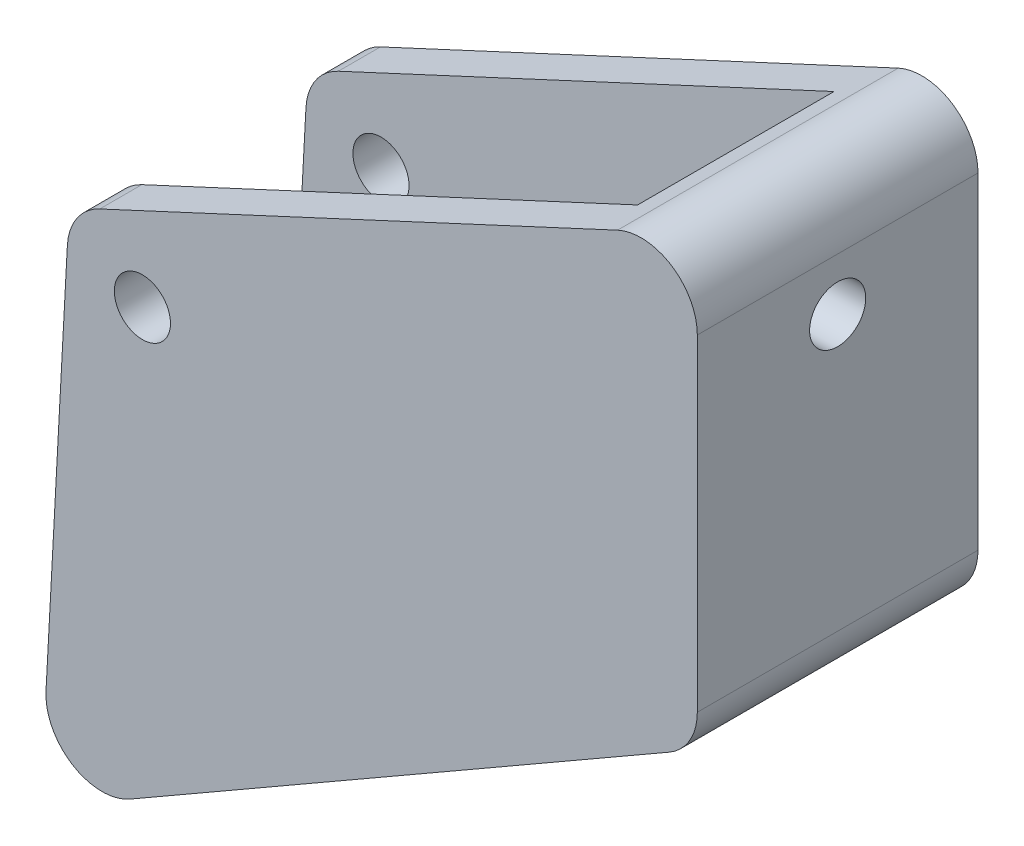
SolidWorks part; units mm, degrees
ref_plane "Plan de face" through (0, 0, 0) normal (0, 0, 1) x (1, 0, 0)
ref_plane "Plan de dessus" through (0, 0, 0) normal (0, 1, 0) x (1, 0, 0)
ref_plane "Plan de droite" through (0, 0, 0) normal (1, 0, 0) x (0, 0, -1)
sketch "Esquisse1" plane through (0, 0, 0) normal (0, 0, 1) x (1, 0, 0)
  line L0 (-16.8159, -61.1738) -> (115.7116, 0.3875) construction
  line L1 (-13.044, 8.8262) -> (98.8497, 60.8028)
  line L2 (-13.044, 8.8262) -> (-18.163, -86.1738)
  line L3 (98.8497, 60.8028) -> (138.7039, -24.9944) construction
  line L4 (-18.163, -86.1738) -> (98.8497, -18.8459)
  line L5 (98.8497, -18.8459) -> (98.8497, 60.8028)
  line L6 (0, 0) -> (0, 59.2463) construction
  dimension "D2" = 70
  dimension "D3" = 62
  dimension "D4" = 13.5
  dimension "D5" = 95
  dimension "D6" = 135
  dimension "D7" = 57
  dimension "D9" = 13.5
  dimension "D10" = 79.6487
extrude "Boss.-Extru.2" add sketch "Esquisse1" along normal mid plane 50 contours L4 L5 L1 L2 region at (40.2075, -9.8823, 0)
sketch "Esquisse2" plane through (0, 0, 0) normal (0, 0, 1) x (1, 0, 0)
  line L0 (-16.8159, -61.1738) -> (82.9463, -14.8325)
  line L1 (-13.044, 8.8262) -> (80.7111, 52.3771)
  line L2 (-13.044, 8.8262) -> (-16.8159, -61.1738)
  line L3 (80.7111, 52.3771) -> (120.1069, -32.4332) construction
  line L5 (82.9463, -14.8325) -> (80.7111, 52.3771)
  line L6 (-13.044, 8.8262) -> (98.8497, 60.8028) construction
  line L7 (-13.044, 8.8262) -> (-18.163, -86.1738) construction
  dimension "D1" = 20
  dimension "D2" = 70
  dimension "D3" = 62
  dimension "D6" = 110
extrude "Enlèv. mat.-Extru.1" cut sketch "Esquisse2" against normal mid plane 35
sketch "Esquisse3" plane through (0, 0, 25) normal (0, 0, 1) x (1, 0, 0)
  line L0 (0, 0) -> (0, 40.5336) construction
  line L1 (-13.044, 8.8262) -> (98.8497, 60.8028) construction
  line L2 (-13.044, 8.8262) -> (-18.163, -86.1738) construction
  circle A0 centre (0, 0) radius 5
  point P2 (0, 32.55)
  dimension "D3" = 10
  dimension "D1" = 13.5
  dimension "D2" = 13.5
  dimension "D4" = 32.55
extrude "Enlèv. mat.-Extru.2" cut sketch "Esquisse3" against normal through all
fillet "Congé1" radius 10 2 edges at (-13.044, 8.8262, -21.25) (-13.044, 8.8262, 21.25)
fillet "Congé2" radius 10 1 edges at (-18.163, -86.1738, 0)
fillet "Congé3" radius 10 2 edges at (98.8497, 60.8028, 0) (98.8497, -18.8459, 0)
ref_axis "Axez" through (0, 0, 0) along (0, 0, 1)
ref_axis "Axe_x" through (104.7735, 0, 0) along (-1, 0, 0)
ref_axis "Axe_y" through (0, -85.0724, 0) along (0, 1, 0)
sketch "Esquisse4" plane through (0, 0, 0) normal (0, 0, 1) x (1, 0, 0)
  point P0 (0, 32.55)
sketch "Esquisse5" plane through (82.3619, 2.7391, 0) normal (-0.9994, -0.0332, 0) x (0, 0, 1)
  circle A0 centre (0, 32.532) radius 5
  point P0 (0, 32.532)
  dimension "D1" = 10
extrude "Enlèv. mat.-Extru.3" cut sketch "Esquisse5" against normal through all
ref_axis "Axe1" through (98.4427, 35.8239, 0) along (-0.9994, -0.0332, 0)
ref_point "Point1"
